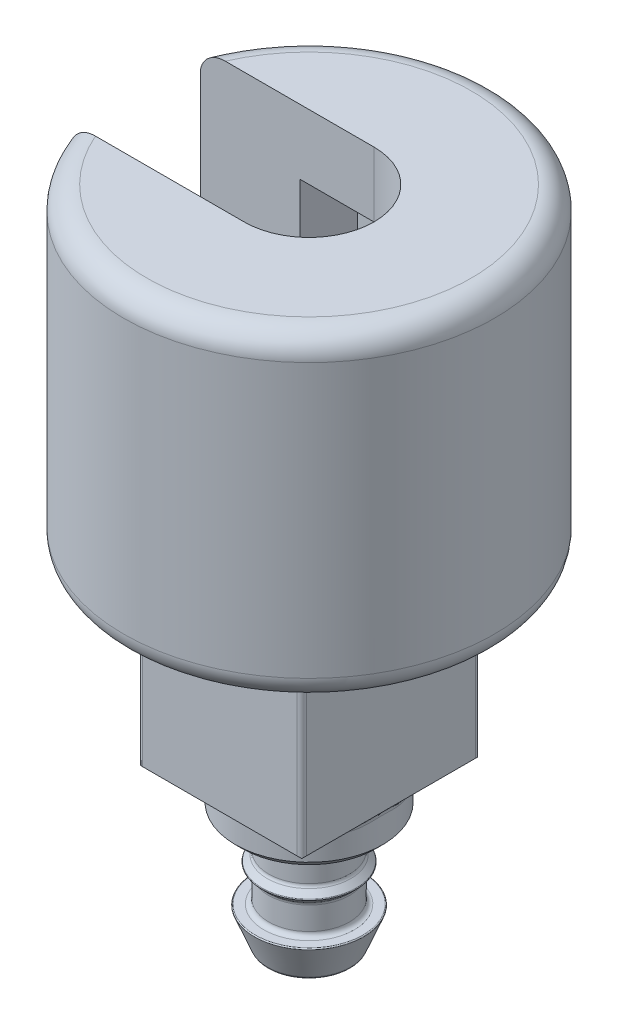
SolidWorks part; units mm, degrees
ref_plane "Front Plane" through (0, 0, 0) normal (0, 0, 1) x (1, 0, 0)
ref_plane "Top Plane" through (0, 0, 0) normal (0, 1, 0) x (1, 0, 0)
ref_plane "Right Plane" through (0, 0, 0) normal (1, 0, 0) x (0, 0, -1)
sketch "Sketch1" plane through (0, 0, 0) normal (0, 0, 1) x (1, 0, 0)
  line L0 (0, 1017.6623) -> (0, 12.7) construction
  line L1 (0, -12.7) -> (4.3656, -12.7)
  line L3 (4.3656, 0) -> (7.9375, 0)
  line L4 (7.9375, 0) -> (7.9375, 3.9688)
  line L8 (0, 3.9688) -> (0, -12.7)
  line L9 (4.3656, -12.7) -> (5.9531, -8.7312)
  line L22 (7.9375, 0) -> (7.9375, 3.9688) construction
  line L25 (7.9375, 6.35) -> (0, 6.35) construction
  line L27 (6.35, 3.9688) -> (7.9375, 3.9688)
  line L32 (5.9531, -8.7312) -> (4.3656, -8.7312)
  line L33 (4.3656, -8.7312) -> (4.3656, -5.5563)
  line L34 (4.3656, -3.9687) -> (5.1594, -4.7625)
  line L35 (5.1594, -4.7625) -> (4.3656, -5.5563)
  line L36 (5.1594, -4.7625) -> (4.3656, -4.7625) construction
  line L37 (4.3656, -3.9687) -> (4.3656, 0)
  line L38 (6.35, 3.9688) -> (0, 3.9688)
  line L40 (0, 3.9688) -> (0, -7.7377) construction
  dimension "D7" = 1.5875
  dimension "D1" = 12.7
  dimension "D2" = 3.9688
  dimension "D6" = 15.875
  dimension "D8" = 8.7312
  dimension "D10" = 7.9375
  dimension "D11" = 45
  dimension "D9" = 0.7937
revolve "Revolve1" add sketch "Sketch1" angle 360 about L0
fillet "Fillet3" radius 0.5 5 edges at (0, -12.7, 4.3656) (0, -8.7313, 4.3656) (0, 0, 4.3656) (0, -3.9688, 4.3656) (0, -5.5562, 4.3656)
fillet "Fillet4" radius 0.0992 2 edges at (0, -8.7313, 5.9531) (0, -4.7625, 5.1594)
ref_plane "Plane1" through (0, 3.9688, 0) normal (0, 1, 0) x (1, 0, 0)
sketch "Sketch2" plane through (0, 3.9688, 0) normal (0, 1, 0) x (1, 0, 0)
  line L0 (0, 9.6273) -> (0, -9.6273) construction
  line L9 (9.0227, 0) -> (-9.0227, 0) construction
  line L11 (8.8366, 9.6273) -> (-8.8366, 9.6273)
  line L12 (8.8366, 9.6273) -> (8.8366, -9.6273)
  line L13 (8.8366, -9.6273) -> (-8.8366, -9.6273)
  line L14 (-8.8366, 9.6273) -> (-8.8366, -9.6273)
  line L15 (8.8366, 9.6273) -> (-8.8366, -9.6273) construction
  line L16 (8.8366, -9.6273) -> (-8.8366, 9.6273) construction
  point P0 (0, 0)
  point P1 (0, 0)
  point P2 (0, 0)
  point P6 (0, 0)
  point P11 (0, 0)
extrude "Boss-Extrude1" add sketch "Sketch2" along normal blind 20
sketch "Sketch3" plane through (0, -12.7, 0) normal (0, -1, 0) x (1, 0, 0)
  circle A0 centre (0, 0) radius 2.413
extrude "Cut-Extrude1" cut sketch "Sketch3" against normal blind 29
sketch "Sketch5" plane through (0, 0, 0) normal (1, 0, 0) x (0, 0, -1)
  line L0 (0, 23.9688) -> (0, 3.9688) construction
  line L1 (9.6273, 23.9688) -> (-9.6273, 23.9688) construction
  line L2 (55, 3.9688) -> (-55, 3.9688) construction
  circle A0 centre (0, 13.9688) radius 2.25
  dimension "D1" = 4.5
extrude "Cut-Extrude3" cut sketch "Sketch5" against normal blind 22.86
chamfer "Chamfer2" distance 0.762 angle 45 5 edges at (8.8366, 3.9688, 0) (0, 3.9688, -9.6273) (-8.8366, 3.9688, 0) (0, 3.9688, 9.6273) (0, 0, 7.9375)
fillet "Fillet6" radius 0.762 1 edges at (0, 3.9688, 7.9375)
sketch "Sketch7" plane through (0, 23.9688, 0) normal (0, 1, 0) x (1, 0, 0)
  circle A0 centre (0, 0) radius 20
  dimension "D1" = 40
extrude "Boss-Extrude2" add sketch "Sketch7" along normal blind 7.5
sketch "Sketch8" plane through (0, 31.4688, 0) normal (0, 1, 0) x (1, 0, 0)
  circle A0 centre (0, 0) radius 12.5
  circle A1 centre (0, 0) radius 20
  circle A2 centre (0, 0) radius 20
  dimension "D1" = 0
extrude "Boss-Extrude3" add sketch "Sketch8" along normal blind 12
ref_plane "Plane2" through (0, 43.4688, 0) normal (0, 1, 0) x (1, 0, 0)
sketch "Sketch9" plane through (0, 43.4688, 0) normal (0, 1, 0) x (1, 0, 0)
  circle A1 centre (0, 0) radius 20
  circle A2 centre (0, 0) radius 20
  dimension "D1" = 0
extrude "Boss-Extrude4" add sketch "Sketch9" along normal blind 15
sketch "Sketch10" plane through (0, 43.4688, 0) normal (0, 1, 0) x (1, 0, 0)
  line L1 (-6.5547, -10.1998) -> (5.556, -10.7764)
  line L2 (5.556, -10.7764) -> (12.1106, -0.5766)
  line L3 (12.1106, -0.5766) -> (6.5547, 10.1998)
  line L4 (6.5547, 10.1998) -> (-5.556, 10.7764)
  line L5 (-5.556, 10.7764) -> (-12.1106, 0.5766)
  line L6 (-12.1106, 0.5766) -> (-6.5547, -10.1998)
  circle A0 centre (0, 0) radius 10.5 construction
  dimension "D1" = 21
extrude "Cut-Extrude4" cut sketch "Sketch10" along normal blind 8
sketch "Sketch11" plane through (0, 0, 0) normal (1, 0, 0) x (0, 0, -1)
  line L0 (0, 58.4688) -> (0, 23.9688) construction
  line L1 (20, 58.4688) -> (-20, 58.4688) construction
  line L2 (-20, 23.9688) -> (20, 23.9688) construction
  line L3 (7, 43.4688) -> (12.5, 43.4688)
  line L5 (-7, 43.4688) -> (-7, 58.4688)
  line L6 (-7, 58.4688) -> (7, 58.4688)
  line L7 (7, 43.4688) -> (7, 58.4688)
  line L8 (-7, 43.4688) -> (7, 58.4688) construction
  line L9 (-7, 58.4688) -> (7, 43.4688) construction
  line L10 (-12.5, 33.4688) -> (12.5, 33.4688)
  line L11 (-12.5, 33.4688) -> (-12.5, 43.4688)
  line L12 (-12.5, 43.4688) -> (-7, 43.4688)
  line L13 (12.5, 33.4688) -> (12.5, 43.4688)
  line L14 (-12.5, 33.4688) -> (12.5, 43.4688) construction
  line L15 (-12.5, 43.4688) -> (12.5, 33.4688) construction
  point P6 (0, 50.9688)
  point P11 (0, 38.4688)
  dimension "D1" = 14
  dimension "D3" = 10
  dimension "D4" = 25
extrude "Cut-Extrude5" cut sketch "Sketch11" against normal through all
sketch "Sketch12" plane through (0, 58.4688, 0) normal (0, 1, 0) x (1, 0, 0)
  circle A0 centre (0, 0) radius 7
  dimension "D1" = 14
extrude "Cut-Extrude6" cut sketch "Sketch12" against normal blind 12 and the other way through all
fillet "Fillet7" radius 2.5 6 edges at (0, 23.9688, -9.6273) (8.8366, 23.9688, 0) (0, 23.9688, 9.6273) (20, 58.4687, 0) (-8.8366, 23.9688, 0) (0, 23.9688, 20)
fillet "Fillet8" radius 0.5 8 edges at (-9.5689, 23.2365, 10.3595) (9.5689, 23.2365, 10.3595) (9.5689, 23.2365, -10.3595) (-9.5689, 23.2365, -10.3595) (-8.8366, 13.0998, 9.6273) (8.8366, 13.0998, 9.6273) (8.8366, 13.0998, -9.6273) (-8.8366, 13.0998, -9.6273)
